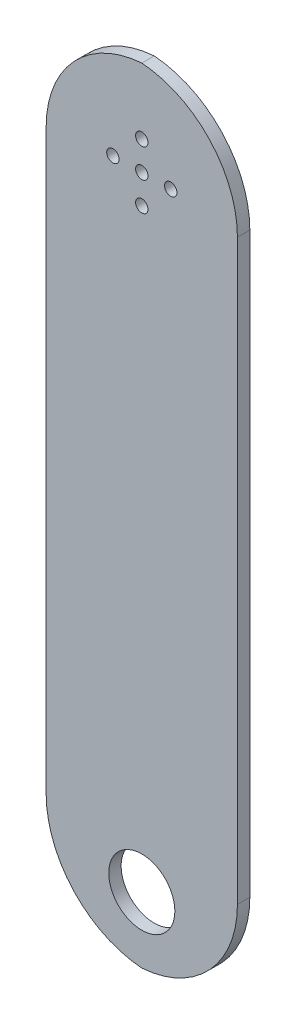
SolidWorks part; units mm, degrees
ref_plane "Front Plane" through (0, 0, 0) normal (0, 0, 1) x (1, 0, 0)
ref_plane "Top Plane" through (0, 0, 0) normal (0, 1, 0) x (1, 0, 0)
ref_plane "Right Plane" through (0, 0, 0) normal (1, 0, 0) x (0, 0, -1)
sketch "Sketch1" plane through (0, 0, 0) normal (0, 0, 1) x (1, 0, 0)
  line L0 (23.15, -94.93) -> (-23.15, -94.93)
  line L1 (23.15, -94.93) -> (23.15, 94.93)
  line L2 (23.15, 94.93) -> (-23.15, 94.93)
  line L3 (-23.15, -94.93) -> (-23.15, 94.93)
  line L4 (23.15, -94.93) -> (-23.15, 94.93) construction
  line L5 (23.15, 94.93) -> (-23.15, -94.93) construction
  circle A1 centre (0, -78.93) radius 8
  circle A2 centre (0, 71.93) radius 7 construction
  circle A3 centre (0, 78.93) radius 1.5
  circle A4 centre (7, 71.93) radius 1.5
  circle A5 centre (0, 64.93) radius 1.5
  circle A6 centre (-7, 71.93) radius 1.5
  circle A7 centre (0, 71.93) radius 1.5
  circle A8 centre (0, 71.93) radius 10.5
  point P0 (0, 0)
  point P9 (0, 0)
  point P21 (0, 0)
  point P22 (0, 0)
  point P23 (0, 0)
  point P24 (0, 0)
  point P25 (0, 0)
  point P26 (0, 0)
  dimension "D3" = 16
  dimension "D6" = 21
  dimension "D7" = 3
  dimension "D9" = 14
  dimension "D1" = 189.86
  dimension "D2" = 46.3
  dimension "D4" = 16
  dimension "D5" = 23.15
  dimension "D8" = 23
extrude "Boss-Extrude1" add sketch "Sketch1" along normal blind 3 contours L3 L0 L1 L2 A8 A1 | A8 A3 A4 A5 A6 A7 region at (0, -1.0971, 0) region at (-10.203, 71.93, 0)
fillet "Fillet1" radius 25 4 edges at (-23.15, -94.93, 1.5) (23.15, -94.93, 1.5) (-23.15, 94.93, 1.5) (23.15, 94.93, 1.5)
